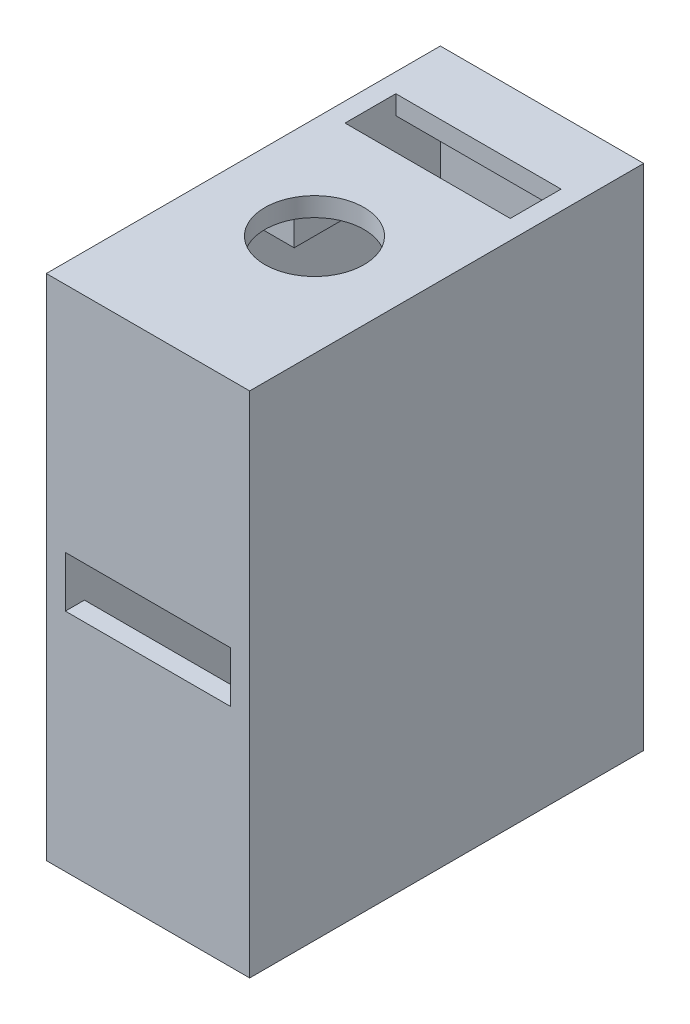
SolidWorks part; units mm, degrees
ref_plane "Front Plane" through (0, 0, 0) normal (0, 0, 1) x (1, 0, 0)
ref_plane "Top Plane" through (0, 0, 0) normal (0, 1, 0) x (1, 0, 0)
ref_plane "Right Plane" through (0, 0, 0) normal (1, 0, 0) x (0, 0, -1)
sketch "Sketch1" plane through (0, 0, 0) normal (0, 1, 0) x (1, 0, 0)
  line L1 (0, 0) -> (16, 0)
  line L2 (0, 0) -> (0, -31)
  line L3 (0, -31) -> (16, -31)
  line L4 (16, 0) -> (16, -31)
  dimension "D1" = 16
  dimension "D2" = 31
extrude "Boss-Extrude1" add sketch "Sketch1" along normal blind 40
shell "Shell1" thickness 1.5 removed face at (8, 0, 15.5)
sketch "Sketch2" plane through (0, 40, 0) normal (0, 1, 0) x (1, 0, 0)
  line L0 (16, 0) -> (0, 0) construction
  line L1 (1.5, -5) -> (14.5, -5)
  line L2 (1.5, -5) -> (1.5, -9)
  line L3 (1.5, -9) -> (14.5, -9)
  line L4 (14.5, -5) -> (14.5, -9)
  line L5 (16, -31) -> (16, 0) construction
  dimension "D1" = 13
  dimension "D2" = 5
  dimension "D3" = 4
  dimension "D4" = 1.5
extrude "Cut-Extrude1" cut sketch "Sketch2" against normal up to vertex (1.5 mm away) up to point (1.5, 38.5, 1.5)
sketch "Sketch3" plane through (0, 0, 0) normal (0, 0, -1) x (-1, 0, 0)
  line L0 (-16, 0) -> (0, 0) construction
  line L2 (-14.5, 10) -> (-14.5, -1)
  line L3 (-14.5, -1) -> (-1.5, -1)
  line L4 (-1.5, 10) -> (-1.5, -1)
  line L5 (-8, 10) -> (-8, 23.3795) construction
  line L6 (0, 40) -> (0, 0) construction
  arc A0 (-14.5, 10) -> (-8, 22.5665) centre (-0.5119, 10.729) cw
  arc A1 (-1.5, 10) -> (-8, 22.5665) centre (-15.4881, 10.729) ccw
  dimension "D4" = 1.5
  dimension "D1" = 13
  dimension "D2" = 1
  dimension "D3" = 11
extrude "Cut-Extrude2" cut sketch "Sketch3" against normal up to vertex (1.5 mm away) up to point (1.5, 0, 1.5)
sketch "Sketch4" plane through (0, 40, 0) normal (0, 1, 0) x (1, 0, 0)
  line L0 (1.5, -9) -> (14.5, -9) construction
  line L1 (16, -31) -> (16, 0) construction
  circle A0 centre (8, -17.9) radius 3.9
  point P4 (0, 0)
  dimension "D1" = 7.8
  dimension "D2" = 8.9
  dimension "D3" = 8
extrude "Cut-Extrude3" cut sketch "Sketch4" against normal up to vertex (1.5 mm away) up to point (1.5, 38.5, 9)
sketch "Sketch6" plane through (0, 38.5, 0) normal (0, -1, 0) x (-1, 0, 0)
  line L1 (-11.5, -9) -> (-14.5, -9)
  line L2 (-11.5, -9) -> (-11.5, -16)
  line L3 (-11.5, -16) -> (-14.5, -16)
  line L4 (-14.5, -9) -> (-14.5, -16)
  line L6 (-8, -9) -> (-8, -6.5435) construction
  line L7 (-1.5, -9) -> (-14.5, -9) construction
  line L8 (-4.5, -16) -> (-1.5, -16)
  line L9 (-1.5, -9) -> (-1.5, -16)
  line L10 (-4.5, -9) -> (-1.5, -9)
  line L11 (-4.5, -9) -> (-4.5, -16)
  dimension "D1" = 3
  dimension "D2" = 7
extrude "Boss-Extrude2" add sketch "Sketch6" along normal blind 2
sketch "Sketch7" plane through (0, 38.5, 0) normal (0, -1, 0) x (-1, 0, 0)
  line L0 (-8, -29.5) -> (-8, -32.4135) construction
  line L1 (-11.3, -20.3) -> (-14.5, -20.3)
  line L2 (-11.3, -20.3) -> (-11.3, -29.5)
  line L3 (-11.3, -29.5) -> (-14.5, -29.5)
  line L4 (-14.5, -20.3) -> (-14.5, -29.5)
  line L5 (-1.5, -29.5) -> (-14.5, -29.5) construction
  line L6 (-4.7, -29.5) -> (-1.5, -29.5)
  line L7 (-1.5, -20.3) -> (-1.5, -29.5)
  line L8 (-4.7, -20.3) -> (-1.5, -20.3)
  line L9 (-4.7, -20.3) -> (-4.7, -29.5)
  dimension "D1" = 3.2
  dimension "D2" = 9.2
extrude "Boss-Extrude3" add sketch "Sketch7" along normal blind 2
sketch "Sketch9" plane through (0, 0, 31) normal (0, 0, 1) x (1, 0, 0)
  line L1 (1.5, 21.7471) -> (14.5, 21.7471)
  line L2 (1.5, 21.7471) -> (1.5, 17.7471)
  line L3 (1.5, 17.7471) -> (14.5, 17.7471)
  line L4 (14.5, 21.7471) -> (14.5, 17.7471)
  line L6 (16, 40) -> (16, 0) construction
  dimension "D1" = 13
  dimension "D2" = 1.5
  dimension "D3" = 4
extrude "Cut-Extrude5" cut sketch "Sketch9" against normal up to vertex (1.5 mm away) up to point (14.5, 36.5, 29.5)
